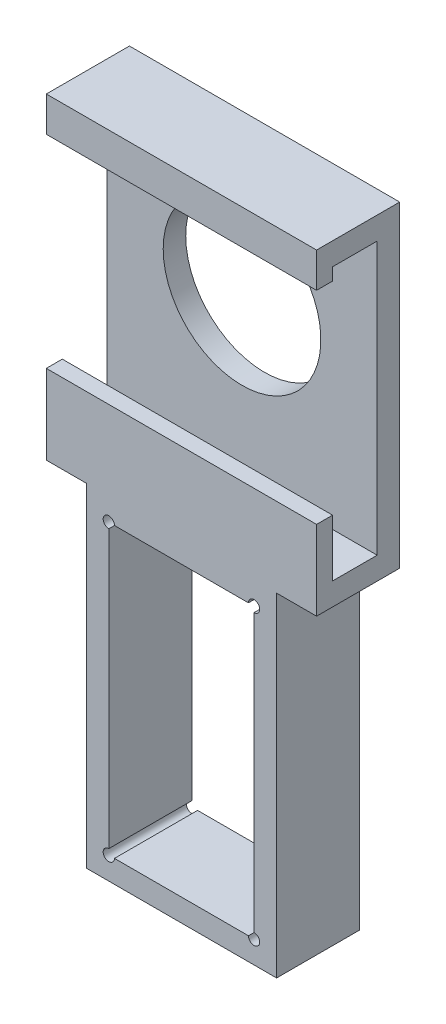
SolidWorks part; units mm, degrees
ref_plane "Front Plane" through (0, 0, 0) normal (0, 0, 1) x (1, 0, 0)
ref_plane "Top Plane" through (0, 0, 0) normal (0, 1, 0) x (1, 0, 0)
ref_plane "Right Plane" through (0, 0, 0) normal (1, 0, 0) x (0, 0, -1)
sketch "Sketch1" plane through (0, 0, 0) normal (0, 0, 1) x (1, 0, 0)
  line L1 (-24, -32.12) -> (24, -32.12)
  line L2 (-24, -32.12) -> (-24, 24.2)
  line L3 (-24, 24.2) -> (24, 24.2)
  line L4 (24, -32.12) -> (24, 24.2)
  line L5 (-24, -32.12) -> (24, 24.2) construction
  line L6 (-24, 24.2) -> (24, -32.12) construction
  line L7 (-16, -28.12) -> (16, -28.12) construction
  point P0 (0, -2.5512)
  point P6 (0, 0)
  point P7 (0, 0)
  point P12 (0, -3.96)
  dimension "D1" = 48
  dimension "D2" = 0
  dimension "D3" = 4
  dimension "D4" = 56.32
extrude "Boss-Extrude1" add sketch "Sketch1" along normal blind 2 and the other way blind 2 contours L3 L4 L1 L2
sketch "Sketch3" plane through (-24, 0, 0) normal (-1, 0, 0) x (0, 0, 1)
  line L0 (2, 24.2) -> (12.76, 24.2)
  line L1 (12.76, 24.2) -> (12.76, 18)
  line L2 (12.76, 15) -> (12.76, 18) construction
  line L3 (24.76, 18) -> (12.76, 18) construction
  line L4 (12.76, 18) -> (9.92, 18)
  line L5 (9.92, 18) -> (9.92, 20.2)
  line L6 (9.92, 20.2) -> (2, 20.2)
  line L8 (2, 20.2) -> (2, 24.2)
  line L9 (3, 20.2) -> (8.92, 20.2) construction
  line L10 (12.76, -18) -> (9.92, -18)
  line L11 (9.92, -18) -> (9.92, -28.12)
  line L12 (9.92, -28.12) -> (2, -28.12)
  line L13 (2, -32.12) -> (2, 24.2) construction
  line L14 (2, -28.12) -> (2, -32.12)
  line L15 (2, -32.12) -> (12.76, -32.12)
  line L16 (12.76, -32.12) -> (12.76, -18)
  line L17 (3, -28.12) -> (8.92, -28.12) construction
extrude "Boss-Extrude2" add sketch "Sketch3" against normal blind 48
sketch "Sketch4" plane through (0, 0, -2) normal (0, 0, -1) x (-1, 0, 0)
  circle A0 centre (0, 0) radius 14
  dimension "D1" = 28
extrude "Cut-Extrude1" cut sketch "Sketch4" against normal through all
sketch "Sketch5" plane through (0, -32.12, 0) normal (0, -1, 0) x (1, 0, 0)
  line L0 (-24, 5.38) -> (24, 5.38) construction
  line L1 (-24, -2) -> (-24, 12.76) construction
  line L2 (24, -2) -> (24, 12.76) construction
  line L3 (0, -2) -> (0, 12.76) construction
  line L4 (-24, -2) -> (24, -2) construction
  line L5 (24, 12.76) -> (-24, 12.76) construction
  circle A0 centre (0, 5.38) radius 2.5 construction
  dimension "D1" = 5
hole_wizard "CSK for #8 Flat Head Machine Screw (100)1" positions "Sketch8" profile "Sketch9" countersink size "#8" standard "ANSI Inch"
sketch "Sketch8" plane through (0, -32.12, 0) normal (0, -1, 0) x (-1, 0, 0)
  point P0 (0, -5.38)
sketch "Sketch9" plane through (0, -32.12, 5.38) normal (1, 0, 0) x (0, 0, -1)
  line L0 (0, 0) -> (0, 9.3507)
  line L1 (0, 9.3507) -> (2.2479, 8)
  line L2 (2.2479, 8) -> (2.2479, 1.6518)
  line L3 (2.2479, 1.6518) -> (4.2164, 0)
  line L5 (4.2164, 0) -> (0, 0)
  line L6 (-2.2479, 1.6518) -> (-4.2164, 0) construction
  line L10 (0, 9.3507) -> (-2.2479, 8) construction
  line L11 (0, -6.35) -> (0, 107.95) construction
  dimension "Hole Dia." = 4.4958
  dimension "Hole Depth" = 8
  dimension "Near C'Sink Dia." = 8.4328
  dimension "Near C'Sink Angle" = 100
  dimension "Drill Angle" = 118
sketch "Sketch10" [suppressed] plane through (0, -32.12, 0) normal (0, -1, 0) x (1, 0, 0)
  line L0 (0, -2) -> (0, 12.76) construction
  line L1 (-16.7, -24.02) -> (16.7, -24.02)
  line L2 (-16.7, -24.02) -> (-16.7, 34.78)
  line L3 (-16.7, 34.78) -> (16.7, 34.78)
  line L4 (16.7, -24.02) -> (16.7, 34.78)
  line L5 (-16.7, -24.02) -> (16.7, 34.78) construction
  line L6 (-16.7, 34.78) -> (16.7, -24.02) construction
  point P0 (0, 5.38)
  dimension "D1" = 33.4
  dimension "D2" = 58.8
extrude "Boss-Extrude3" [suppressed] add sketch "Sketch10" along normal blind 58.8 separate body
shell "Shell1" [suppressed] thickness 4
sketch "Sketch11" [suppressed] plane through (0, 0, -20.02) normal (0, 0, 1) x (1, 0, 0)
  line L1 (-12.7, -36.12) -> (12.7, -36.12)
  line L2 (-12.7, -36.12) -> (-12.7, -86.92)
  line L3 (-12.7, -86.92) -> (12.7, -86.92)
  line L4 (12.7, -36.12) -> (12.7, -86.92)
extrude "Cut-Extrude3" [suppressed] cut sketch "Sketch11" against normal through all
sketch "Sketch12" [suppressed] plane through (0, -90.92, 0) normal (0, -1, 0) x (1, 0, 0)
  circle A0 centre (0, 5.38) radius 2.5
extrude "Cut-Extrude4" [suppressed] cut sketch "Sketch12" against normal through all
sketch "Sketch13" plane through (0, 0, 12.76) normal (0, 0, 1) x (1, 0, 0)
  line L0 (-12.9, -36.12) -> (12.9, -36.12)
  line L1 (-12.7, -36.32) -> (12.7, -36.32) construction
  line L2 (-12.7, -36.32) -> (-12.7, -87.12) construction
  line L3 (-12.7, -87.12) -> (12.7, -87.12) construction
  line L4 (12.7, -36.32) -> (12.7, -87.12) construction
  line L5 (12.9, -36.12) -> (12.9, -87.32)
  line L6 (-12.9, -87.32) -> (12.9, -87.32)
  line L7 (-12.9, -36.12) -> (-12.9, -87.32)
  line L9 (-16.9, -32.12) -> (16.9, -32.12)
  line L10 (16.9, -32.12) -> (16.9, -91.32)
  line L11 (-16.9, -91.32) -> (16.9, -91.32)
  line L12 (-16.9, -32.12) -> (-16.9, -91.32)
  line L13 (-24, -32.12) -> (24, -32.12) construction
  point P14 (0, -87.32)
  dimension "D1" = 25.4
  dimension "D2" = 50.8
  dimension "D3" = 0.2
  dimension "D4" = 4
extrude "Boss-Extrude4" add sketch "Sketch13" against normal up to surface (14.76 mm away) up to face at (-14, 0, -2)
sketch "Sketch14" plane through (0, 0, 12.76) normal (0, 0, 1) x (1, 0, 0)
  circle A0 centre (-12.9, -36.12) radius 1
  circle A1 centre (12.9, -36.12) radius 1
  circle A2 centre (12.9, -87.32) radius 1
  circle A3 centre (-12.9, -87.32) radius 1
  dimension "D1" = 2
  dimension "D2" = 2
  dimension "D3" = 2
  dimension "D4" = 2
extrude "Cut-Extrude5" cut sketch "Sketch14" against normal through all
equation "\"D2@Sketch14\"=\"D1@Sketch14\""
equation "\"D4@Sketch14\"=\"D1@Sketch14\""
